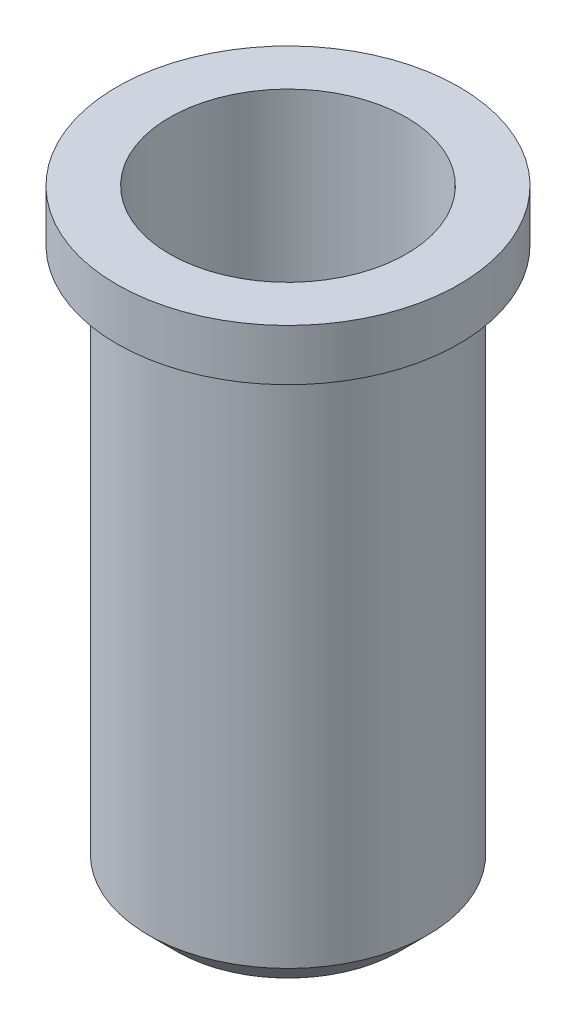
SolidWorks part; units mm, degrees
ref_plane "Front Plane" through (0, 0, 0) normal (0, 0, 1) x (1, 0, 0)
ref_plane "Top Plane" through (0, 0, 0) normal (0, 1, 0) x (1, 0, 0)
ref_plane "Right Plane" through (0, 0, 0) normal (1, 0, 0) x (0, 0, -1)
sketch "Sketch1" plane through (0, 0, 0) normal (0, 0, 1) x (1, 0, 0)
  line L0 (0, 0) -> (0, 8.4047) construction
  line L1 (0, 0) -> (0.9906, 0)
  line L2 (0, 0) -> (0, 0.254)
  line L4 (1.2446, 0.254) -> (1.2446, 4.953)
  line L8 (1.0541, 5.4102) -> (1.0541, 0.8382)
  line L9 (1.0541, 5.4102) -> (1.524, 5.4102)
  line L10 (1.0541, 5.4102) -> (1.0541, 7.9798)
  line L11 (1.2446, 4.953) -> (1.524, 4.953)
  line L12 (1.524, 5.4102) -> (1.524, 4.953)
  line L13 (1.2446, 0.254) -> (0.9906, 0)
  line L14 (1.0541, 0.8382) -> (0, 0.254)
  point P5 (0, 0.254)
  dimension "D1" = 0.4572
  dimension "D2" = 1.524
  dimension "D3" = 5.4102
  dimension "D4" = 1.2446
  dimension "D5" = 0.254
  dimension "D6" = 0.254
  dimension "D7" = 4.572
  dimension "D8" = 0.1905
  dimension "D9" = 0.254
revolve "Revolve1" add sketch "Sketch1" angle 360 about L0 region at (0.0562, 0.127, 0)
